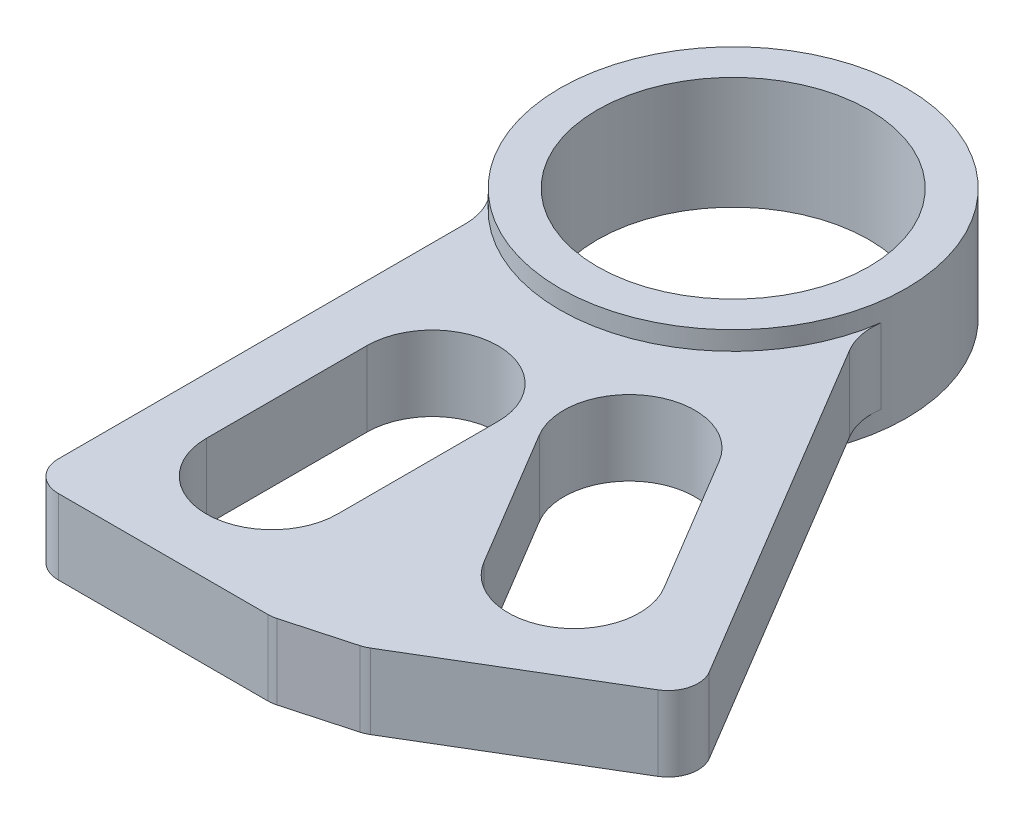
SolidWorks part; units mm, degrees
material "AISI 4130 Steel, normalized at 870C"
ref_plane "Front Plane" through (0, 0, 0) normal (0, 0, 1) x (1, 0, 0)
ref_plane "Top Plane" through (0, 0, 0) normal (0, 1, 0) x (1, 0, 0)
ref_plane "Right Plane" through (0, 0, 0) normal (1, 0, 0) x (0, 0, -1)
sketch "Sketch1" plane through (0, 0, 0) normal (0, 1, 0) x (1, 0, 0)
  line L0 (0, 0) -> (0, -49.3903) construction
  line L1 (0, 0) -> (25.3391, -42.395) construction
  line L2 (0, -39.0716) -> (0, -25.4826) construction
  line L3 (-5.5562, -39.0716) -> (-5.5562, -25.4826)
  line L4 (5.5563, -39.0716) -> (5.5563, -25.4826)
  line L5 (20.0452, -33.5377) -> (13.0735, -21.8734) construction
  line L6 (15.2759, -36.3883) -> (8.3042, -24.7239)
  line L7 (24.8145, -30.6871) -> (17.8428, -19.0228)
  line L8 (0, -49.3903) -> (0, -44.6278) construction
  line L9 (25.3391, -42.395) -> (22.8958, -38.307) construction
  line L10 (-10.3187, -49.3903) -> (10.3188, -49.3903)
  line L11 (16.4818, -47.6889) -> (34.1964, -37.101)
  line L12 (-10.3187, -49.3903) -> (-10.3187, -10.4432)
  line L13 (10.3188, -49.3903) -> (10.3188, -37.3774)
  line L14 (34.1964, -37.101) -> (14.215, -3.6702)
  line L15 (16.4818, -47.6889) -> (10.3188, -37.3774)
  line L16 (185.4189, -310.2251) -> (14.7508, -24.6796) construction
  line L17 (10.3188, -49.3903) -> (16.4818, -47.6889)
  line L22 (0, 0) -> (10.3188, -37.3774) construction
  circle A0 centre (0, 0) radius 11.5062
  circle A1 centre (0, 0) radius 14.6812
  arc A2 (-5.5562, -39.0716) -> (5.5563, -39.0716) centre (0, -39.0716) ccw
  arc A3 (5.5563, -25.4826) -> (-5.5562, -25.4826) centre (0, -25.4826) ccw
  arc A4 (15.2759, -36.3883) -> (24.8145, -30.6871) centre (20.0452, -33.5377) ccw
  arc A5 (17.8428, -19.0228) -> (8.3042, -24.7239) centre (13.0735, -21.8734) ccw
  point P8 (0, -32.2771)
  point P13 (16.5594, -27.7055)
  point P25 (0, -49.3903)
  point P27 (25.3391, -42.395)
  dimension "D2" = 29.3624
  dimension "D3" = 4.7625
  dimension "D4" = 4.7625
  dimension "D5" = 13.589
  dimension "D6" = 49.3903
  dimension "D7" = 20.6375
extrude "Bearing_Insert_Extrude" add sketch "Sketch1" along normal mid plane 9.525 contours A1 A0 region at (-5.4988, 0, -13.1636)
extrude "Apex_Slot_Insert_Extrude" add sketch "Sketch1<4>" along normal mid plane 6.35 contours A1 L12 L10 L13 L15 L11 L14 A5 L7 A4 L6 A3 L4 A2 L3 | L13 L17 L15 region at (8.33, 0, 30.1737) region at (12.3731, 0, 44.8188)
sketch "Sketch1<4>" plane through (0, 0, 0) normal (0, 1, 0) x (1, 0, 0) same geometry as "Sketch1"
fillet "Fillet1" radius 5.08 2 edges at (14.215, 0, 3.6702) (-10.3187, 0, 10.4432)
fillet "Fillet2" radius 2.54 4 edges at (34.1964, 0, 37.101) (-10.3187, 0, 49.3903) (16.4818, 0, 47.6889) (10.3188, 0, 49.3903)
equation "\"Apex_thickness\"= .25"
equation "\"Bearing_diameter\"= 0.906in"
equation "\"A-arm_angle\"= 39.1893"
equation "\"D1@Sketch1\"=\"Bearing_diameter\""
equation "\"D1@Apex_Slot_Insert_Extrude\"=\"Apex_thickness\""
